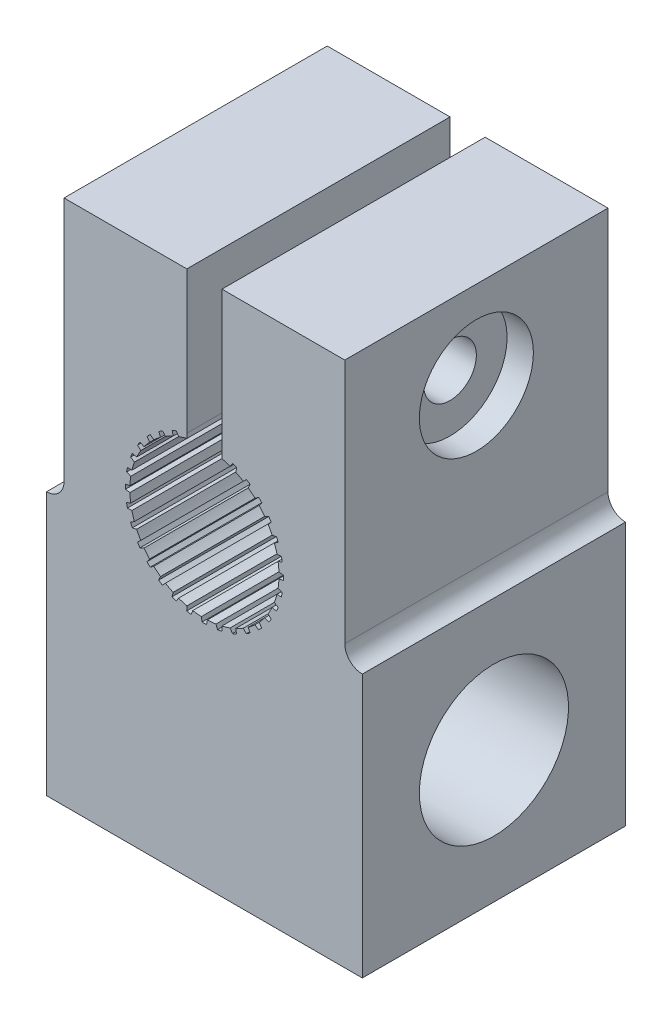
SolidWorks part; units mm, degrees
ref_plane "Piano frontale" through (0, 0, 0) normal (0, 0, 1) x (1, 0, 0)
ref_plane "Piano superiore" through (0, 0, 0) normal (0, 1, 0) x (1, 0, 0)
ref_plane "Piano destro" through (0, 0, 0) normal (1, 0, 0) x (0, 0, -1)
sketch "Schizzo1" plane through (0, 0, 0) normal (0, 0, 1) x (1, 0, 0)
  line L0 (0, 0) -> (0, 15)
  line L1 (0, 15) -> (1, 15)
  line L2 (1, 15) -> (1, 30)
  line L3 (1, 30) -> (8, 30)
  line L4 (8, 30) -> (8, 21.8875)
  line L5 (10, 30) -> (10, 21.8875)
  line L6 (10, 30) -> (17, 30)
  line L7 (17, 30) -> (17, 15)
  line L8 (17, 15) -> (18, 15)
  line L9 (18, 15) -> (18, 0)
  line L10 (18, 0) -> (0, 0)
  line L11 (9, 0) -> (9, 37.7654) construction
  line L12 (0, 7.5) -> (18, 7.5) construction
  line L13 (8, 21.8875) -> (8.0082, 21.6326)
  line L14 (7.5345, 21.4893) -> (7.4, 21.7059)
  line L16 (7.5345, 21.4893) -> (8.0387, 20.6771) construction
  line L17 (8.0387, 20.6771) -> (8.0082, 21.6326) construction
  line L22 (10.6061, 21.7036) -> (10.4713, 21.4872)
  line L23 (9.9978, 21.6312) -> (10.0063, 21.886)
  line L24 (11.3953, 21.3095) -> (11.2209, 21.1236)
  line L25 (10.7846, 21.3572) -> (10.8427, 21.6054)
  line L26 (12.0925, 20.769) -> (11.8851, 20.6207)
  line L27 (11.5028, 20.9349) -> (11.6082, 21.1671)
  line L28 (12.6708, 20.1029) -> (12.4385, 19.9978)
  line L29 (12.1248, 20.3806) -> (12.2735, 20.5878)
  line L30 (13.1081, 19.3367) -> (12.8597, 19.279)
  line L31 (12.6268, 19.7156) -> (12.813, 19.8898)
  line L32 (13.3875, 18.5) -> (13.1326, 18.4918)
  line L33 (12.9893, 18.9655) -> (13.2059, 19.1)
  line L34 (13.4983, 17.6248) -> (13.2467, 17.6665)
  line L35 (13.1986, 18.1591) -> (13.4373, 18.2487)
  line L36 (13.4362, 16.7449) -> (13.1976, 16.8348)
  line L37 (13.2465, 17.3273) -> (13.4981, 17.3687)
  line L38 (13.2036, 15.8939) -> (12.9872, 16.0287)
  line L39 (13.1312, 16.5022) -> (13.386, 16.4937)
  line L40 (12.8095, 15.1047) -> (12.6236, 15.2791)
  line L41 (12.8572, 15.7154) -> (13.1054, 15.6573)
  line L42 (12.269, 14.4075) -> (12.1207, 14.6149)
  line L43 (12.4349, 14.9972) -> (12.6671, 14.8918)
  line L44 (11.6029, 13.8292) -> (11.4978, 14.0615)
  line L45 (11.8806, 14.3752) -> (12.0878, 14.2265)
  line L46 (10.8367, 13.3919) -> (10.779, 13.6403)
  line L47 (11.2156, 13.8732) -> (11.3898, 13.687)
  line L48 (10, 13.1125) -> (9.9918, 13.3674)
  line L49 (10.4655, 13.5107) -> (10.6, 13.2941)
  line L50 (9.1248, 13.0017) -> (9.1665, 13.2533)
  line L51 (9.6591, 13.3014) -> (9.7487, 13.0627)
  line L52 (8.2449, 13.0638) -> (8.3348, 13.3024)
  line L53 (8.8273, 13.2535) -> (8.8687, 13.0019)
  line L54 (7.3939, 13.2964) -> (7.5287, 13.5128)
  line L55 (8.0022, 13.3688) -> (7.9937, 13.114)
  line L56 (6.6047, 13.6905) -> (6.7791, 13.8764)
  line L57 (7.2154, 13.6428) -> (7.1573, 13.3946)
  line L58 (5.9075, 14.231) -> (6.1149, 14.3793)
  line L59 (6.4972, 14.0651) -> (6.3918, 13.8329)
  line L60 (5.3292, 14.8971) -> (5.5615, 15.0022)
  line L61 (5.8752, 14.6194) -> (5.7265, 14.4122)
  line L62 (4.8919, 15.6633) -> (5.1403, 15.721)
  line L63 (5.3732, 15.2844) -> (5.187, 15.1102)
  line L64 (4.6125, 16.5) -> (4.8674, 16.5082)
  line L65 (5.0107, 16.0345) -> (4.7941, 15.9)
  line L66 (4.5017, 17.3752) -> (4.7533, 17.3335)
  line L67 (4.8014, 16.8409) -> (4.5627, 16.7513)
  line L68 (4.5638, 18.2551) -> (4.8024, 18.1652)
  line L69 (4.7535, 17.6727) -> (4.5019, 17.6313)
  line L70 (4.7964, 19.1061) -> (5.0128, 18.9713)
  line L71 (4.8688, 18.4978) -> (4.614, 18.5063)
  line L72 (5.1905, 19.8953) -> (5.3764, 19.7209)
  line L73 (5.1428, 19.2846) -> (4.8946, 19.3427)
  line L74 (5.731, 20.5925) -> (5.8793, 20.3851)
  line L75 (5.5651, 20.0028) -> (5.3329, 20.1082)
  line L76 (6.3971, 21.1708) -> (6.5022, 20.9385)
  line L77 (6.1194, 20.6248) -> (5.9122, 20.7735)
  line L78 (7.1633, 21.6081) -> (7.221, 21.3597)
  line L79 (6.7844, 21.1268) -> (6.6102, 21.313)
  line L80 (8.3409, 21.6986) -> (8.2513, 21.9373) [skipped]
  line L81 (8.8752, 21.9983) -> (8.8335, 21.7467) [skipped]
  line L82 (9.1727, 21.7465) -> (9.1313, 21.9981) [skipped]
  line L83 (9.7551, 21.9362) -> (9.6652, 21.6976) [skipped]
  arc A0 (10, 21.8875) -> (10.0063, 21.886) centre (9, 17.5) cw
  arc A1 (8.0082, 21.6326) -> (7.5345, 21.4893) centre (9, 17.5) ccw
  arc A2 (10.6061, 21.7036) -> (10.8427, 21.6054) centre (9, 17.5) cw
  arc A3 (11.3953, 21.3095) -> (11.6082, 21.1671) centre (9, 17.5) cw
  arc A4 (10.4713, 21.4872) -> (9.9978, 21.6312) centre (9, 17.5) ccw
  arc A5 (11.2209, 21.1236) -> (10.7846, 21.3572) centre (9, 17.5) ccw
  arc A6 (11.8851, 20.6207) -> (11.5028, 20.9349) centre (9, 17.5) ccw
  arc A7 (12.4385, 19.9978) -> (12.1248, 20.3806) centre (9, 17.5) ccw
  arc A8 (12.8597, 19.279) -> (12.6268, 19.7156) centre (9, 17.5) ccw
  arc A9 (13.1326, 18.4918) -> (12.9893, 18.9655) centre (9, 17.5) ccw
  arc A10 (13.2467, 17.6665) -> (13.1986, 18.1591) centre (9, 17.5) ccw
  arc A11 (13.1976, 16.8348) -> (13.2465, 17.3273) centre (9, 17.5) ccw
  arc A12 (12.9872, 16.0287) -> (13.1312, 16.5022) centre (9, 17.5) ccw
  arc A13 (12.6236, 15.2791) -> (12.8572, 15.7154) centre (9, 17.5) ccw
  arc A14 (12.1207, 14.6149) -> (12.4349, 14.9972) centre (9, 17.5) ccw
  arc A15 (11.4978, 14.0615) -> (11.8806, 14.3752) centre (9, 17.5) ccw
  arc A16 (10.779, 13.6403) -> (11.2156, 13.8732) centre (9, 17.5) ccw
  arc A17 (9.9918, 13.3674) -> (10.4655, 13.5107) centre (9, 17.5) ccw
  arc A18 (9.1665, 13.2533) -> (9.6591, 13.3014) centre (9, 17.5) ccw
  arc A19 (8.3348, 13.3024) -> (8.8273, 13.2535) centre (9, 17.5) ccw
  arc A20 (7.5287, 13.5128) -> (8.0022, 13.3688) centre (9, 17.5) ccw
  arc A21 (6.7791, 13.8764) -> (7.2154, 13.6428) centre (9, 17.5) ccw
  arc A22 (6.1149, 14.3793) -> (6.4972, 14.0651) centre (9, 17.5) ccw
  arc A23 (5.5615, 15.0022) -> (5.8752, 14.6194) centre (9, 17.5) ccw
  arc A24 (5.1403, 15.721) -> (5.3732, 15.2844) centre (9, 17.5) ccw
  arc A25 (4.8674, 16.5082) -> (5.0107, 16.0345) centre (9, 17.5) ccw
  arc A26 (4.7533, 17.3335) -> (4.8014, 16.8409) centre (9, 17.5) ccw
  arc A27 (4.8024, 18.1652) -> (4.7535, 17.6727) centre (9, 17.5) ccw
  arc A28 (5.0128, 18.9713) -> (4.8688, 18.4978) centre (9, 17.5) ccw
  arc A29 (5.3764, 19.7209) -> (5.1428, 19.2846) centre (9, 17.5) ccw
  arc A30 (5.8793, 20.3851) -> (5.5651, 20.0028) centre (9, 17.5) ccw
  arc A31 (6.5022, 20.9385) -> (6.1194, 20.6248) centre (9, 17.5) ccw
  arc A32 (7.221, 21.3597) -> (6.7844, 21.1268) centre (9, 17.5) ccw
  arc A33 (8.8335, 21.7467) -> (8.3409, 21.6986) centre (9, 17.5) ccw [skipped]
  arc A34 (9.6652, 21.6976) -> (9.1727, 21.7465) centre (9, 17.5) ccw [skipped]
  arc A35 (12.0925, 20.769) -> (12.2735, 20.5878) centre (9, 17.5) cw
  arc A36 (12.6708, 20.1029) -> (12.813, 19.8898) centre (9, 17.5) cw
  arc A37 (13.1081, 19.3367) -> (13.2059, 19.1) centre (9, 17.5) cw
  arc A38 (13.3875, 18.5) -> (13.4373, 18.2487) centre (9, 17.5) cw
  arc A39 (13.4983, 17.6248) -> (13.4981, 17.3687) centre (9, 17.5) cw
  arc A40 (13.4362, 16.7449) -> (13.386, 16.4937) centre (9, 17.5) cw
  arc A41 (13.2036, 15.8939) -> (13.1054, 15.6573) centre (9, 17.5) cw
  arc A42 (12.8095, 15.1047) -> (12.6671, 14.8918) centre (9, 17.5) cw
  arc A43 (12.269, 14.4075) -> (12.0878, 14.2265) centre (9, 17.5) cw
  arc A44 (11.6029, 13.8292) -> (11.3898, 13.687) centre (9, 17.5) cw
  arc A45 (10.8367, 13.3919) -> (10.6, 13.2941) centre (9, 17.5) cw
  arc A46 (10, 13.1125) -> (9.7487, 13.0627) centre (9, 17.5) cw
  arc A47 (9.1248, 13.0017) -> (8.8687, 13.0019) centre (9, 17.5) cw
  arc A48 (8.2449, 13.0638) -> (7.9937, 13.114) centre (9, 17.5) cw
  arc A49 (7.3939, 13.2964) -> (7.1573, 13.3946) centre (9, 17.5) cw
  arc A50 (6.6047, 13.6905) -> (6.3918, 13.8329) centre (9, 17.5) cw
  arc A51 (5.9075, 14.231) -> (5.7265, 14.4122) centre (9, 17.5) cw
  arc A52 (5.3292, 14.8971) -> (5.187, 15.1102) centre (9, 17.5) cw
  arc A53 (4.8919, 15.6633) -> (4.7941, 15.9) centre (9, 17.5) cw
  arc A54 (4.6125, 16.5) -> (4.5627, 16.7513) centre (9, 17.5) cw
  arc A55 (4.5017, 17.3752) -> (4.5019, 17.6313) centre (9, 17.5) cw
  arc A56 (4.5638, 18.2551) -> (4.614, 18.5063) centre (9, 17.5) cw
  arc A57 (4.7964, 19.1061) -> (4.8946, 19.3427) centre (9, 17.5) cw
  arc A58 (5.1905, 19.8953) -> (5.3329, 20.1082) centre (9, 17.5) cw
  arc A59 (5.731, 20.5925) -> (5.9122, 20.7735) centre (9, 17.5) cw
  arc A60 (6.3971, 21.1708) -> (6.6102, 21.313) centre (9, 17.5) cw
  arc A61 (7.1633, 21.6081) -> (7.4, 21.7059) centre (9, 17.5) cw
  point P148 (9, 17.5)
  dimension "D3" = 4.5
  dimension "D4" = 10
  dimension "D5" = 15
  dimension "D8" = 0.25
  dimension "D9" = 0.6
  dimension "D1" = 15
  dimension "D2" = 2
  dimension "D6" = 18
  dimension "D7" = 1
  dimension "D10" = 30
  dimension "D11" = 32
extrude "Estrusione-Estrusione1" add sketch "Schizzo1" along normal mid plane 15 contours A51 L61 A23 L60 A52 L63 A24 L62 A53 L65 A25 L64 A54 L67 A26 L66 A55 L69 A27 L68 A56 L71 A28 L70 A57 L73 A29 L72 A58 L75 A30 L74 A59 L77 A31 L76 A60 L79 A32 L78 A61 L14 A1 L13 L4 L3 L2 L1 L0 L10 L9 L8 L7 L6 L5 A0 L23 A4 L22 A2 L25 A5 L24 A3 L27 A6 L26 A35 L29 A7 L28 A36 L31 A8 L30 A37 L33 A9 L32 A38 L35 A10 L34 A39 L37 A11 L36 A40 L39 A12 L38 A41 L41 A13 L40 A42 L43 A14 L42 A43 L45 A15 L44 A44 L47 A16 L46 A45 L49 A17 L48 A46 L51 A18 L50 A47 L53 A19 L52 A48 L55 A20 L54 A49 L57 A21 L56 A50 L59 A22 L58
sketch "Schizzo2" plane through (17, 0, 0) normal (1, 0, 0) x (0, 0, -1)
  line L0 (-7.5, 30) -> (7.5, 30) construction
  line L1 (-7.5, 30) -> (7.5, 30)
  line L2 (0, 30) -> (0, 25) construction
  circle A0 centre (0, 25) radius 1.5
  dimension "D1" = 3
  dimension "D3" = 5
extrude "Taglio-Estrusione1" cut sketch "Schizzo2" against normal through all both and the other way through all contours A0
sketch "Schizzo5" plane through (17, 0, 0) normal (1, 0, 0) x (0, 0, -1)
  circle A0 centre (0, 25) radius 1.5 construction
  circle A1 centre (0, 25) radius 1.5
  circle A2 centre (0, 25) radius 3.25
  dimension "D1" = 6.5
extrude "Taglio-Estrusione2" cut sketch "Schizzo5" against normal blind 1.5
sketch "Schizzo6" plane through (1, 0, 0) normal (-1, 0, 0) x (0, 0, 1)
  line L1 (3, 25) -> (1.5, 27.5981)
  line L2 (1.5, 27.5981) -> (-1.5, 27.5981)
  line L3 (-1.5, 27.5981) -> (-3, 25)
  line L4 (-3, 25) -> (-1.5, 22.4019)
  line L5 (-1.5, 22.4019) -> (1.5, 22.4019)
  line L6 (1.5, 22.4019) -> (3, 25)
  circle A0 centre (0, 25) radius 2.5981 construction
  dimension "D1" = 6
extrude "Taglio-Estrusione3" cut sketch "Schizzo6" against normal blind 2.4
sketch "Schizzo7" plane through (0, 0, 0) normal (-1, 0, 0) x (0, 0, 1)
  line L0 (-7.5, 15) -> (7.5, 0) construction
  circle A0 centre (0, 7.5) radius 4.25
  dimension "D1" = 8.5
extrude "Taglio-Estrusione4" cut sketch "Schizzo7" against normal through all
fillet "Raccordo1" radius 1 1 edges at (17, 15, 0)
fillet "Raccordo2" radius 1 1 edges at (1, 15, 0)
